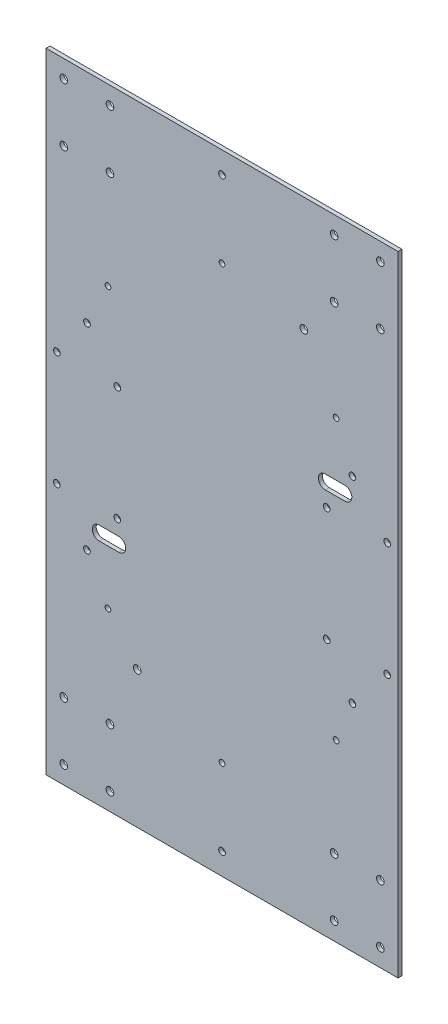
SolidWorks part; units mm, degrees
ref_plane "Alzado" through (0, 0, 0) normal (0, 0, 1) x (1, 0, 0)
ref_plane "Planta" through (0, 0, 0) normal (0, 1, 0) x (1, 0, 0)
ref_plane "Vista lateral" through (0, 0, 0) normal (1, 0, 0) x (0, 0, -1)
sketch "Croquis1" plane through (0, 0, 0) normal (0, 0, 1) x (1, 0, 0)
  line L1 (-89.5, -160) -> (89.5, -160)
  line L2 (-89.5, -160) -> (-89.5, 160)
  line L3 (-89.5, 160) -> (89.5, 160)
  line L4 (89.5, -160) -> (89.5, 160)
  line L5 (-89.5, -160) -> (89.5, 160) construction
  line L6 (-89.5, 160) -> (89.5, -160) construction
  point P0 (0, 0)
  dimension "D1" = 179
  dimension "D2" = 320
extrude "Saliente-Extruir1" add sketch "Croquis1" along normal blind 2
sketch "lineas guia" plane through (0, 0, 2) normal (0, 0, 1) x (1, 0, 0)
  line L0 (-89.5, 160) -> (89.5, -160) construction
  line L1 (89.5, 0) -> (-89.5, 0) construction
  line L2 (-89.5, -160) -> (89.5, 160) construction
  line L3 (-89.5, 160) -> (-89.5, -160) construction
  point P14 (0, 0)
sketch "superior bores" plane through (0, 0, 2) normal (0, 0, 1) x (1, 0, 0)
  point P0 (66.31, 49.42)
  point P1 (0, 149)
  point P5 (-68.69, 49.42)
  point P6 (-68.69, -50.58)
  point P7 (0, -149)
  point P8 (66.31, -50.58)
  dimension "D2" = 149
  dimension "D3" = 149
  dimension "D5" = 49.42
  dimension "D6" = 66.31
  dimension "D4" = 2
  dimension "D1" = 2
sketch "mid bores" plane through (0, 0, 2) normal (0, 0, 1) x (1, 0, 0)
  point P0 (-58, 71)
  point P1 (0, 110)
  point P2 (0, -110)
  point P4 (58, 71)
  point P6 (58, -71)
  point P8 (-58, -71)
  dimension "D1" = 110
  dimension "D2" = 58
  dimension "D3" = 71
  dimension "D4" = 110
  dimension "D5" = 2
  dimension "D6" = 2
sketch "regul bores" plane through (0, 0, 2) normal (0, 0, 1) x (1, 0, 0)
  point P0 (-84, 29)
  point P1 (-53.2526, 29)
  point P3 (-53.2526, -29)
  point P5 (-84, -29)
  point P7 (53.2526, 29)
  point P9 (84, 29)
  point P11 (84, -29)
  point P13 (53.2526, -29)
sketch "wheel bores" plane through (0, 0, 2) normal (0, 0, 1) x (1, 0, 0)
  line L0 (-89.5, 160) -> (-89.5, -160) construction
  line L1 (-89.5, -160) -> (89.5, -160) construction
  point P0 (-80.5, -121.42)
  point P1 (-57, -121.42)
  point P2 (-57, -151)
  point P3 (-80.5, -151)
  point P4 (0, 0)
  point P5 (0, 0)
  point P6 (0, 0)
  point P7 (0, 0)
  dimension "D1" = 23.5
  dimension "D2" = 29.58
  dimension "D3" = 9
  dimension "D4" = 9
sketch "power supply bores" plane through (0, 0, 0) normal (0, 0, -1) x (-1, 0, 0)
  point P0 (-41.6, 101.785)
  point P1 (43.2, -90.415)
hole_wizard "Taladro de margen para M31" positions "Croquis3" profile "Croquis4" hole size "M3" standard "Ansi Metric" end condition through all
sketch "Croquis3" plane through (0, 0, 2) normal (0, 0, 1) x (1, 0, 0)
  point P0 (0, 149)
  point P3 (-68.69, 49.42)
  point P6 (-68.69, -50.58)
  point P9 (0, -149)
  point P12 (66.31, -50.58)
  point P15 (66.31, 49.42)
sketch "Croquis4" plane through (0, 149, 2) normal (1, 0, 0) x (0, -1, 0)
  line L0 (0, 0) -> (0, 2)
  line L1 (0, 2) -> (1.7, 2)
  line L2 (1.7, 2) -> (1.7, 0)
  line L5 (1.7, 0) -> (0, 0)
  line L11 (0, -6.35) -> (0, 107.95) construction
  dimension "Diámetro de taladro hasta el siguiente" = 3.4
  dimension "Profundidad de taladro hasta el siguiente" = 2
hole_wizard "Taladro de margen para M2.51" positions "Croquis5" profile "Croquis6" hole size "M2.5" standard "Ansi Metric" end condition through all
sketch "Croquis5" plane through (0, 0, 2) normal (0, 0, 1) x (1, 0, 0)
  point P0 (0, 110)
  point P3 (-58, 71)
  point P6 (-58, -71)
  point P9 (0, -110)
  point P12 (58, -71)
  point P15 (58, 71)
sketch "Croquis6" plane through (0, 110, 2) normal (1, 0, 0) x (0, -1, 0)
  line L0 (0, 0) -> (0, 2)
  line L1 (0, 2) -> (1.45, 2)
  line L2 (1.45, 2) -> (1.45, 0)
  line L5 (1.45, 0) -> (0, 0)
  line L11 (0, -6.35) -> (0, 107.95) construction
  dimension "Diámetro de taladro hasta el siguiente" = 2.9
  dimension "Profundidad de taladro hasta el siguiente" = 2
hole_wizard "Taladro de margen para M32" positions "Croquis8" profile "Croquis9" hole size "M3" standard "Ansi Metric" end condition through all
sketch "Croquis8" plane through (0, 0, 2) normal (0, 0, 1) x (1, 0, 0)
  point P0 (-84, 29)
  point P3 (-84, -29)
  point P6 (-53.2526, 29)
  point P9 (-53.2526, -29)
  point P12 (53.2526, 29)
  point P15 (84, 29)
  point P18 (84, -29)
  point P21 (53.2526, -29)
sketch "Croquis9" plane through (-84, 29, 2) normal (1, 0, 0) x (0, -1, 0)
  line L0 (0, 0) -> (0, 2)
  line L1 (0, 2) -> (1.7, 2)
  line L2 (1.7, 2) -> (1.7, 0)
  line L5 (1.7, 0) -> (0, 0)
  line L11 (0, -6.35) -> (0, 107.95) construction
  dimension "Diámetro de taladro hasta el siguiente" = 3.4
  dimension "Profundidad de taladro hasta el siguiente" = 2
sketch "Croquis10" plane through (0, 0, 2) normal (0, 0, 1) x (1, 0, 0)
  line L0 (-62.5, -40) -> (-52.5, -40) construction
  line L1 (-62.5, -36.5) -> (-52.5, -36.5)
  line L2 (-62.5, -43.5) -> (-52.5, -43.5)
  line L3 (52.5, 40) -> (62.5, 40) construction
  line L4 (52.5, 43.5) -> (62.5, 43.5)
  line L5 (52.5, 36.5) -> (62.5, 36.5)
  arc A0 (-62.5, -36.5) -> (-62.5, -43.5) centre (-62.5, -40) ccw
  arc A1 (-52.5, -43.5) -> (-52.5, -36.5) centre (-52.5, -40) ccw
  arc A2 (52.5, 43.5) -> (52.5, 36.5) centre (52.5, 40) ccw
  arc A3 (62.5, 36.5) -> (62.5, 43.5) centre (62.5, 40) ccw
  point P2 (-57.5, -40)
  point P8 (57.5, 40)
  dimension "D1" = 7
  dimension "D2" = 10
  dimension "D3" = 57.5
  dimension "D4" = 40
  dimension "D5" = 7
  dimension "D6" = 10
  dimension "D7" = 40
  dimension "D8" = 57.5
extrude "Cortar-Extruir1" cut sketch "Croquis10" against normal through all
hole_wizard "Taladro de margen para M3.51" positions "Croquis12" profile "Croquis13" hole size "M3.5" standard "Ansi Metric" end condition through all
sketch "Croquis12" plane through (0, 0, 2) normal (0, 0, 1) x (1, 0, 0)
  point P0 (-80.5, -121.42)
  point P3 (-57, -121.42)
  point P6 (-57, -151)
  point P9 (-80.5, -151)
sketch "Croquis13" plane through (-80.5, -121.42, 2) normal (1, 0, 0) x (0, -1, 0)
  line L0 (0, 0) -> (0, 2)
  line L1 (0, 2) -> (1.95, 2)
  line L2 (1.95, 2) -> (1.95, 0)
  line L5 (1.95, 0) -> (0, 0)
  line L11 (0, -6.35) -> (0, 107.95) construction
  dimension "Diámetro de taladro hasta el siguiente" = 3.9
  dimension "Profundidad de taladro hasta el siguiente" = 2
mirror "Simetría3" about plane through (0, 0, 0) normal (0, 1, 0) of "Taladro de margen para M3.51"
mirror "Simetría4" about plane through (0, 0, 0) normal (1, 0, 0) of "Simetría3"
hole_wizard "Taladro de margen para M3.52" positions "Croquis15" profile "Croquis16" hole size "M3.5" standard "Ansi Metric" end condition through all
sketch "Croquis15" plane through (0, 0, 0) normal (0, 0, -1) x (-1, 0, 0)
  point P0 (-41.6, 101.785)
  point P3 (43.2, -90.415)
sketch "Croquis16" plane through (41.6, 101.785, 0) normal (1, 0, 0) x (0, 1, 0)
  line L0 (0, 0) -> (0, 2)
  line L1 (0, 2) -> (1.95, 2)
  line L2 (1.95, 2) -> (1.95, 0)
  line L5 (1.95, 0) -> (0, 0)
  line L11 (0, -6.35) -> (0, 107.95) construction
  dimension "Diámetro de taladro hasta el siguiente" = 3.9
  dimension "Profundidad de taladro hasta el siguiente" = 2
